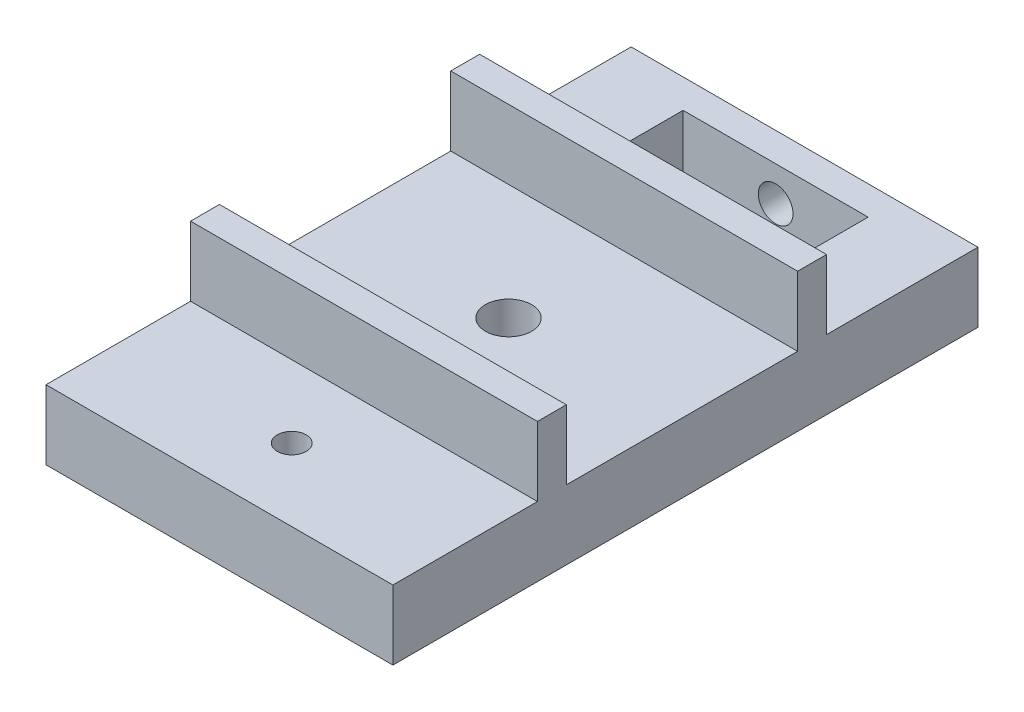
SolidWorks part; units mm, degrees
ref_plane "Front" through (0, 0, 0) normal (0, 0, 1) x (1, 0, 0)
ref_plane "Top" through (0, 0, 0) normal (0, 1, 0) x (1, 0, 0)
ref_plane "Right" through (0, 0, 0) normal (1, 0, 0) x (0, 0, -1)
sketch "Sketch1" plane through (0, 0, 0) normal (0, 1, 0) x (1, 0, 0)
  line L0 (0, -20) -> (0, -22.5)
  line L1 (0, 0) -> (-30, 0)
  line L2 (0, 0) -> (0, -20)
  line L3 (0, -20) -> (-30, -20)
  line L4 (-30, 0) -> (-30, -20)
  line L5 (0, -22.5) -> (-30, -22.5)
  line L6 (-30, -22.5) -> (-30, -20)
  line L7 (0, 0) -> (-7, 0)
  line L8 (-30, 0) -> (0, 0)
  line L9 (-30, 0) -> (-30, 2.5)
  line L10 (-30, 2.5) -> (0, 2.5)
  line L11 (0, 0) -> (0, 2.5)
  line L12 (-30, 0) -> (-23, 0)
  line L13 (-30, 2.5) -> (-30, 13.1)
  line L14 (-30, 13.1) -> (0, 13.1)
  line L15 (0, 13.1) -> (0, 2.5)
  line L16 (0, 13.1) -> (0, 15.6)
  line L17 (0, 15.6) -> (-30, 15.6)
  line L18 (-30, 15.6) -> (-30, 13.1)
  line L19 (-7, 0) -> (-7, 15.6)
  line L20 (-23, 0) -> (-23, 15.6)
  dimension "D1" = 20
  dimension "D2" = 2.5
  dimension "D3" = 2.5
  dimension "D4" = 30
  dimension "D5" = 7
  dimension "D6" = 7
  dimension "D7" = 10.6
  dimension "D8" = 2.5
extrude "Boss-Extrude1" add sketch "Sketch1" along normal blind 6 contours L1 L8 L4 L3 L2 | L6 L5 L0 L3 | L20 L1 L19 L10 | L19 L1 L11 L10 | L19 L10 L15 L14 | L19 L14 L16 L17 | L20 L14 L19 L17 | L14 L20 L17 L18 | L10 L20 L14 L13 | L8 L20 L10 L9 region at (-15, 0, 10) region at (-15, 0, 21.25) region at (-3.5, 0, -1.25) region at (-15, 0, -1.25) region at (-3.5, 0, -7.8) region at (-26.5, 0, -1.25) region at (-3.5, 0, -14.35) region at (-26.5, 0, -7.8) region at (-15, 0, -14.35) region at (-26.5, 0, -14.35)
extrude "Boss-Extrude2" add sketch "Sketch1<3>" along normal blind 12 contours L19 L1 L11 L10 | L20 L1 L19 L10 | L6 L5 L0 L3 | L8 L20 L10 L9 region at (-15, 0, 21.25) region at (-3.5, 0, -1.25) region at (-15, 0, -1.25) region at (-26.5, 0, -1.25)
sketch "Sketch1<3>" plane through (0, 0, 0) normal (0, 1, 0) x (1, 0, 0) same geometry as "Sketch1"
sketch "Sketch3" plane through (0, 0, -15.6) normal (0, 0, -1) x (-1, 0, 0)
  line L0 (30, 3) -> (23, 3)
  line L1 (30, 6) -> (30, 0) construction
  line L2 (23, 3) -> (15, 3)
  circle A0 centre (15, 3) radius 1.5
  dimension "D1" = 7
  dimension "D2" = 8
extrude "Cut-Extrude2" cut sketch "Sketch3" against normal blind 15 contours A0
ref_plane "Plane1" through (0, 0, 10) normal (0, 0, -1) x (-1, 0, 0)
sketch "Sketch2" plane through (0, 6, 0) normal (0, 1, 0) x (1, 0, 0)
  line L0 (-30, -10) -> (0, -10)
  line L1 (-30, 0) -> (-30, -20) construction
  line L2 (0, 0) -> (0, -20) construction
  circle A0 centre (-15, -10) radius 2
extrude "Cut-Extrude1" cut sketch "Sketch2" against normal through all contours L0 A0 | L0 A0 region at (-15, 6, 9.1512) region at (-15, 6, 10.8488)
sketch "Sketch5" plane through (0, 0, 0) normal (0, -1, 0) x (1, 0, 0)
  line L0 (-30, 22.5) -> (-25, 22.5)
  line L1 (-30, 22.5) -> (0, 22.5)
  line L2 (-30, 22.5) -> (-30, 32.5)
  line L3 (0, 22.5) -> (0, 32.5)
  line L4 (-30, 32.5) -> (0, 32.5)
  line L5 (-25, 22.5) -> (-25, 32.5)
  line L6 (-25, 32.5) -> (-5, 32.5)
  line L7 (-5, 32.5) -> (-5, 22.5)
  line L8 (-5, 22.5) -> (0, 22.5)
  line L9 (-30, 32.5) -> (-30, 35)
  line L10 (-30, 35) -> (0, 35)
  line L11 (0, 35) -> (0, 32.5)
  line L12 (-15, 35) -> (-15, 22.5)
  circle A0 centre (-15, 28.75) radius 1.25
  line M7 (0, 22.5) -> (-30, 22.5)
  dimension "D1" = 10
  dimension "D2" = 5
  dimension "D3" = 5
  dimension "D4" = 2.5
extrude "Boss-Extrude3" add sketch "Sketch5" against normal blind 6 contours L5 L4 L2 M7 | L11 L10 L9 L4 | L4 L7 L3 M7 | L7 L4 L5 L1 | A0 L12 L4 L5 M7 | L12 L10 L9 L4 region at (-27.5, 0, 27.5) region at (-20.1125, 0, 27.4685) region at (-22.5, 0, 33.75) region at (-9.8875, 0, 27.4685) region at (-2.5, 0, 27.5) region at (-7.5, 0, 33.75)
